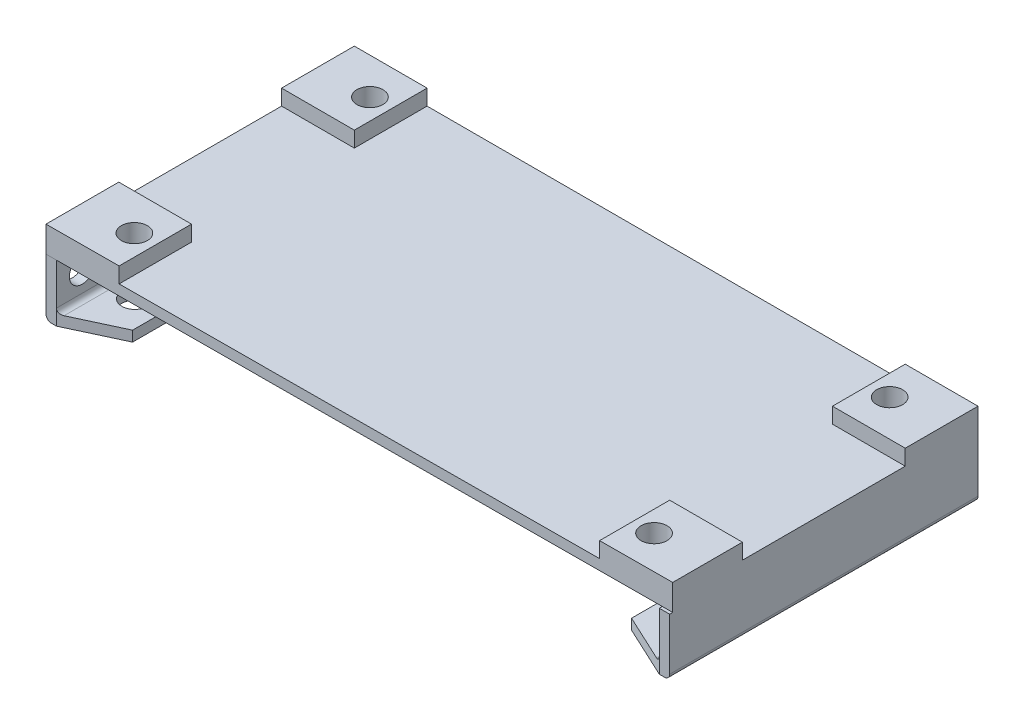
SolidWorks part; units mm, degrees
note: The reader was unsure of these and kept them because the rebuilt part matched: shared geometry of "Sketch3<5>".
material "ABS"
ref_plane "Front Plane" through (0, 0, 0) normal (0, 0, 1) x (1, 0, 0)
ref_plane "Top Plane" through (0, 0, 0) normal (0, 1, 0) x (1, 0, 0)
ref_plane "Right Plane" through (0, 0, 0) normal (1, 0, 0) x (0, 0, -1)
sketch "Sketch1" plane through (0, 0, 0) normal (0, 1, 0) x (1, 0, 0)
  line L0 (-49.0619, -3.3366) -> (-49.0619, -53.3366)
  line L1 (-49.0619, -53.3366) -> (-59.0619, -57.9996)
  line L2 (-59.0619, -57.9996) -> (-59.0619, 1.3265)
  line L3 (-59.0619, 1.3265) -> (-49.0619, -3.3366)
  dimension "D1" = 115
  dimension "D2" = 115
  dimension "D3" = 50
  dimension "D4" = 10
extrude "Boss-Extrude1" add sketch "Sketch1" along normal blind 2
sketch "Sketch2" plane through (-59.0619, 0, 0) normal (-1, 0, 0) x (0, 0, 1)
  line L0 (-1.3265, 0) -> (-1.3265, 11)
  line L1 (-1.3265, 11) -> (57.9996, 11)
  line L2 (57.9996, 11) -> (57.9996, 0)
  line L3 (57.9996, 0) -> (-1.3265, 0)
  line L4 (28.3366, 11) -> (28.3366, -12.7839) construction
  dimension "D1" = 90
  dimension "D2" = 11
extrude "Boss-Extrude2" add sketch "Sketch2" along normal blind 2
fillet "Fillet1" radius 1 2 edges at (-61.0619, 0, 28.3366) (-59.0619, 2, 28.3366)
sketch "Sketch3" plane through (0, 11, 0) normal (0, 1, 0) x (1, 0, 0)
  line L0 (-61.0619, 1.3265) -> (58.9381, 1.3265)
  line L1 (58.9381, -12.6735) -> (58.9381, -57.4134)
  line L2 (58.9381, -57.4134) -> (-61.0619, -57.9996)
  line L3 (-61.0619, -57.9996) -> (-61.0619, -12.6735)
  line L4 (-1.0619, -57.7065) -> (-1.0619, 16.926) construction
  line L5 (-61.0619, -28.3366) -> (21.5138, -28.3366) construction
  line L6 (58.9381, -12.6735) -> (44.9381, -12.6735)
  line L7 (-61.0619, 1.3265) -> (-47.0619, 1.3265)
  line L9 (-61.0619, -12.6735) -> (-47.0619, -12.6735)
  line L10 (-47.0619, 1.3265) -> (-47.0619, -12.6735)
  line L11 (58.9381, 1.3265) -> (44.9381, 1.3265)
  line L13 (44.9381, 1.3265) -> (44.9381, -12.6735)
  line L15 (58.9381, -43.9996) -> (44.9381, -43.9996)
  line L16 (44.9381, -57.9996) -> (44.9381, -43.9996)
  line L17 (-61.0619, -43.9996) -> (-47.0619, -43.9996)
  line L18 (-47.0619, -57.9996) -> (-47.0619, -43.9996)
  line L19 (-61.0619, -43.9996) -> (-61.0619, -57.9996)
  line L20 (58.9381, -43.9996) -> (58.9381, -57.4134)
  line L23 (58.9381, 1.3265) -> (58.9381, -12.6735)
  line L24 (-61.0619, 1.3265) -> (-61.0619, -12.6735)
  circle A0 centre (-51.0619, -5.6735) radius 2.5
  circle A2 centre (-51.0619, -50.9996) radius 2.5
  circle A3 centre (48.9381, -50.9996) radius 2.5
  circle A4 centre (48.9381, -5.6735) radius 2.5
  line M4 (-59.0619, -57.9996) -> (-59.0619, 1.3265)
  line M6 (-59.0619, 1.3265) -> (-61.0619, 1.3265)
  line M7 (-61.0619, 1.3265) -> (-61.0619, -57.9996)
  dimension "D2" = 5
  dimension "D1" = 120
  dimension "D3" = 7
  dimension "D4" = 10
  dimension "D5" = 14
  dimension "D6" = 14
extrude "Boss-Extrude3" add sketch "Sketch3" along normal blind 2 contours L18 L2 L16 L15 L1 L6 L13 L0 L10 L9 L17 M4 | L23 L0 L13 L6 A4 | L16 L2 L1 L15 A3 | L2 L18 L17 A2 M4 | L10 L0 L9 A0 M4 | L17 L9 M7 M4 | L9 M7 M4 M6 | L17 L3 L2 M4 | L24
ref_plane "Plane1" through (-1.0619, 0, 0) normal (-1, 0, 0) x (0, 0, 1)
mirror "Mirror1" about plane through (-1.0619, 0, 0) normal (-1, 0, 0) of "Boss-Extrude1", "Boss-Extrude2"
mirror "Mirror2" about plane through (-1.0619, 0, 0) normal (-1, 0, 0) of "Boss-Extrude1"
fillet "Fillet3" radius 1 2 edges at (56.9381, 2, 28.3366) (58.9381, 0, 28.3366)
sketch "Sketch4" plane through (-61.0619, 0, 0) normal (-1, 0, 0) x (0, 0, 1)
  line L0 (-1.3265, 13) -> (-1.3265, 1) construction
  line L1 (28.3366, 13) -> (28.3366, -12.5526) construction
  circle A0 centre (3.6735, 7) radius 2.5
  circle A1 centre (52.9996, 7) radius 2.5
  point P5 (-1.3265, 7)
  dimension "D1" = 5
  dimension "D2" = 5
extrude "Cut-Extrude1" cut sketch "Sketch4" against normal up to surface (2 mm away) up to face at (-59.0619, 7.8, 34.2672)
extrude "Boss-Extrude5" add sketch "Sketch3<5>" along normal blind 3 from surface contours L10 L0 L9 A0 M4 | L9 M7 M4 M6 | L2 L18 L17 A2 M4 | L17 L3 L2 M4 | L16 L2 L1 L15 A3 | L23 L0 L13 L6 A4 | L24
sketch "Sketch3<5>" plane through (0, 11, 0) normal (0, 1, 0) x (1, 0, 0) same geometry as "Sketch3"
sketch "Sketch5" plane through (0, 0, 0) normal (0, -1, 0) x (1, 0, 0)
  line L1 (-59.0619, 57.9996) -> (-49.0619, 53.3366) construction
  line L2 (-60.0619, 28.3366) -> (61.1887, 28.3366) construction
  line L3 (-60.0619, 57.9996) -> (-60.0619, -1.3265) construction
  line L4 (-1.0619, 8.25) -> (-1.0619, -8.25) construction
  circle A0 centre (-54.0619, 47.9039) radius 2.5
  circle A1 centre (51.9381, 47.9039) radius 2.5
  circle A2 centre (51.9381, 8.7692) radius 2.5
  circle A3 centre (-54.0619, 8.7692) radius 2.5
  point P5 (-54.0619, 55.6681)
  dimension "D1" = 5
extrude "Cut-Extrude2" cut sketch "Sketch5" against normal up to surface (2 mm away) up to face at (-53.5619, 2, 28.3366)
